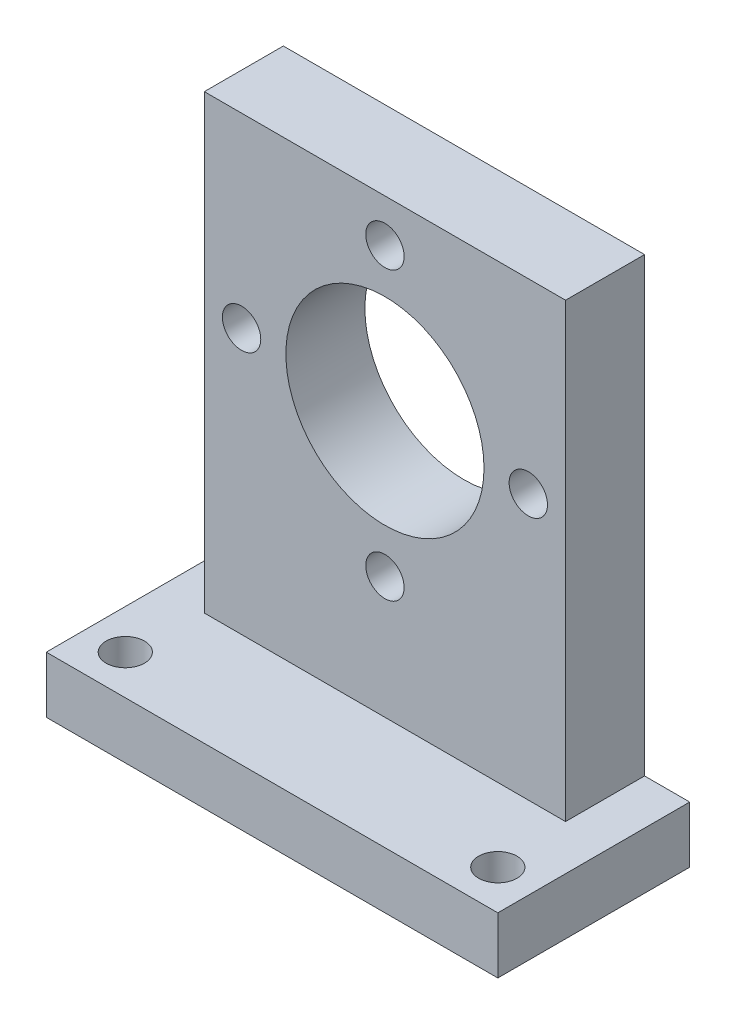
SolidWorks part; units mm, degrees
ref_plane "Front Plane" through (0, 0, 0) normal (0, 0, 1) x (1, 0, 0)
ref_plane "Top Plane" through (0, 0, 0) normal (0, 1, 0) x (1, 0, 0)
ref_plane "Right Plane" through (0, 0, 0) normal (1, 0, 0) x (0, 0, -1)
sketch "Sketch1" plane through (0, 0, 0) normal (0, 1, 0) x (1, 0, 0)
  line L1 (-20, 13.5) -> (20, 13.5)
  line L2 (-20, 13.5) -> (-20, -13.5)
  line L3 (-20, -13.5) -> (20, -13.5)
  line L4 (20, 13.5) -> (20, -13.5)
  line L5 (-20, 13.5) -> (20, -13.5) construction
  line L6 (-20, -13.5) -> (20, 13.5) construction
  line L7 (-16, 3.5) -> (16, 3.5)
  line L8 (-16, 3.5) -> (-16, -3.5)
  line L9 (-16, -3.5) -> (16, -3.5)
  line L10 (16, 3.5) -> (16, -3.5)
  line L11 (-16, 3.5) -> (16, -3.5) construction
  line L12 (-16, -3.5) -> (16, 3.5) construction
  point P0 (0, 0)
  point P6 (0, 0)
  dimension "D1" = 40
  dimension "D2" = 27
  dimension "D3" = 7
  dimension "D4" = 32
extrude "Boss-Extrude1" add sketch "Sketch1" along normal blind 5 contours L10 L7 L8 L9 | L2 L1 L4 L3 region at (0, 0, 0)
extrude "Boss-Extrude2" add sketch "Sketch1<3>" along normal blind 45 contours L10 L7 L8 L9 region at (0, 0, 0)
sketch "Sketch1<3>" plane through (0, 0, 0) normal (0, 1, 0) x (1, 0, 0) same geometry as "Sketch1"
sketch "Sketch2" plane through (0, 0, 3.5) normal (0, 0, 1) x (1, 0, 0)
  line L0 (-20, 5) -> (20, 5) construction
  circle A0 centre (0, 28.5) radius 8.7757
  dimension "D1" = 17.5514
  dimension "D2" = 23.5
extrude "Cut-Extrude1" cut sketch "Sketch2" against normal up to next
sketch "Sketch4" plane through (0, 0, 3.5) normal (0, 0, 1) x (1, 0, 0)
  line L0 (0, 45) -> (0, 28.5) construction
  line L1 (-16, 45) -> (16, 45) construction
  circle A0 centre (0, 41.2) radius 1.7
  circle A1 centre (0, 28.5) radius 8.7757 construction
  circle A2 centre (12.7, 28.5) radius 1.7
  circle A3 centre (0, 15.8) radius 1.7
  circle A4 centre (-12.7, 28.5) radius 1.7
  point P18 (0, 28.5)
  dimension "D2" = 3.4
  dimension "D1" = 12.7
  dimension "D3" = 4
extrude "Cut-Extrude2" cut sketch "Sketch4" against normal up to next
sketch "Sketch5" plane through (0, 5, 0) normal (0, 1, 0) x (1, 0, 0)
  line L1 (-20, 13.5) -> (20, 13.5) construction
  line L2 (-20, 13.5) -> (-20, -13.5) construction
  line L3 (-20, -13.5) -> (20, -13.5) construction
  line L4 (0, 13.5) -> (0, -13.5) construction
  circle A0 centre (-16.5, 10) radius 1.7
  circle A2 centre (-16.5, -10) radius 1.7
  circle A4 centre (16.5, -10) radius 1.7
  circle A5 centre (16.5, 10) radius 1.7
  dimension "D3" = 3.4
  dimension "D1" = 3.5
  dimension "D2" = 3.5
  dimension "D4" = 3.5
extrude "Cut-Extrude3" cut sketch "Sketch5" against normal up to next
sketch "Sketch7" plane through (0, 5, 0) normal (0, 1, 0) x (1, 0, 0)
  line L0 (-20, 13.5) -> (-20, -13.5) construction
  line L1 (-20, 3.5) -> (20, 3.5)
  line L2 (-20, 3.5) -> (-20, 13.5)
  line L3 (-20, 13.5) -> (20, 13.5)
  line L4 (20, 3.5) -> (20, 13.5)
  line L5 (-16, 3.5) -> (16, 3.5) construction
extrude "Cut-Extrude5" cut sketch "Sketch7" against normal up to next
sketch "Sketch8" plane through (0, 0, -3.5) normal (0, 0, -1) x (-1, 0, 0)
  line L0 (-12.7, 28.5) -> (-12.7, 2.5) construction
  line L1 (0, 0) -> (0, 13.0763) construction
  line L5 (-20, 5) -> (-20, 0) construction
  circle A0 centre (-12.7, 2.5) radius 1.7
  circle A1 centre (12.7, 2.5) radius 1.7
  circle A2 centre (-12.7, 28.5) radius 1.7 construction
  point P9 (-20, 2.5)
extrude "Cut-Extrude6" cut sketch "Sketch8" against normal blind 6.35
